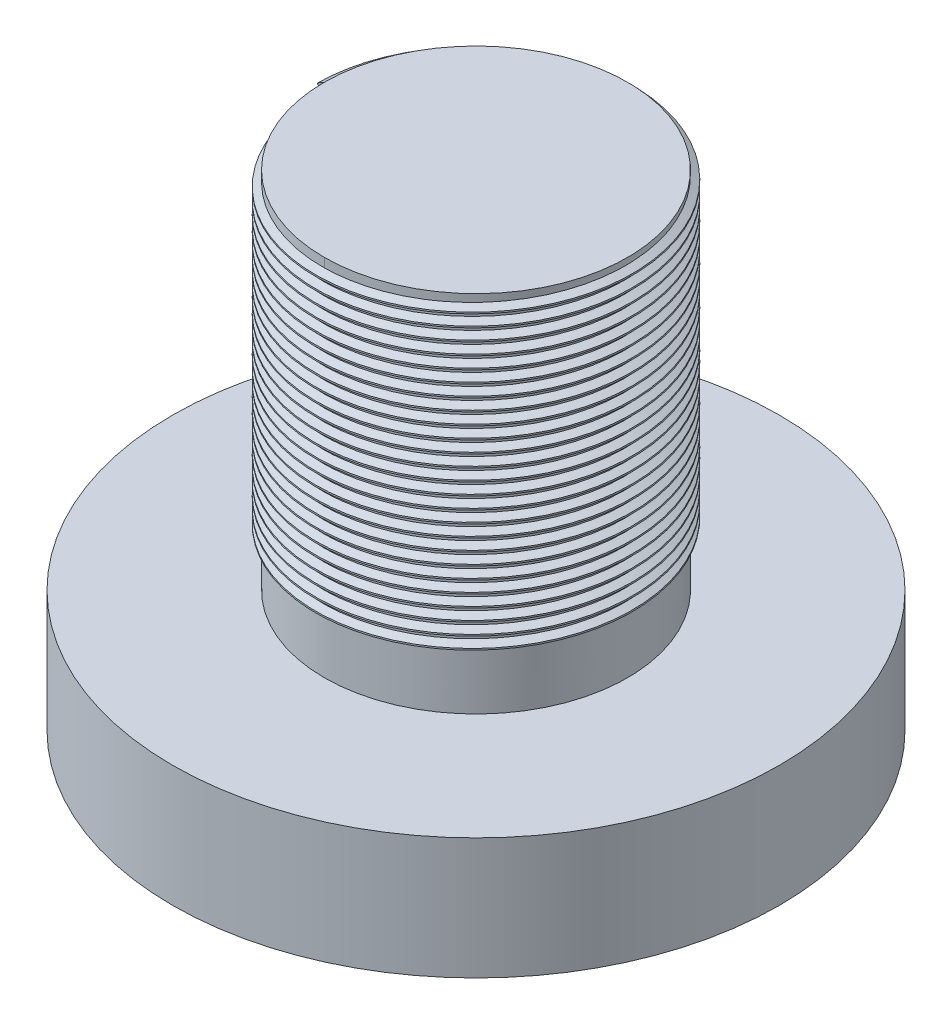
SolidWorks part; units mm, degrees
material "Ст 3 ГОСТ 380-88"
ref_plane "Front Plane" through (0, 0, 0) normal (0, 0, 1) x (1, 0, 0)
ref_plane "Top Plane" through (0, 0, 0) normal (0, 1, 0) x (1, 0, 0)
ref_plane "Right Plane" through (0, 0, 0) normal (1, 0, 0) x (0, 0, -1)
sketch "Sketch1" plane through (0, 0, 0) normal (1, 0, 0) x (0, 0, -1)
  line L0 (0, 54.3307) -> (0, -61.2205) construction
  line L1 (-25, 30) -> (-25, -30)
  line L2 (-25, -30) -> (-50, -30)
  line L3 (-50, -30) -> (-50, -50)
  line L4 (-50, -50) -> (0, -50)
  line L5 (-25, 30) -> (0, 30)
  line L6 (0, -50) -> (0, 30)
  point P10 (-25, 0)
  dimension "D1" = 50
  dimension "D2" = 20
  dimension "D3" = 100
  dimension "D4" = 80
revolve "Revolve1" add sketch "Sketch1" angle 360 about L0
thread "Thread1" pitch 2 method extrude profile "Thread Profile1" start angle 0, offset 0, length 50, pitch 2, diameter 50
ref_plane "Plane1" through (-25, 30, 0) normal (0, 0, 1) x (-1, 0, 0)
sketch "Thread Profile1" plane through (-25, 30, 0) normal (0, 0, 1) x (-1, 0, 0)
  line L0 (0, 0) -> (0, 2) construction
  line L1 (0, 0) -> (1.0825, 0.625)
  line L2 (1.0825, 0.625) -> (1.0825, 0.875)
  line L3 (1.0825, 0.875) -> (0, 1.5)
  line L4 (1.0825, 0.75) -> (0, 0.75) construction
  line L11 (0, 0) -> (0, 1.5)
  point P2 (0, 0)
  dimension "Pitch" = 2
  dimension "Profile_Angle" = 60
  dimension "Profile_Land" = 0.25
  dimension "Profile_Height" = 1.0825
